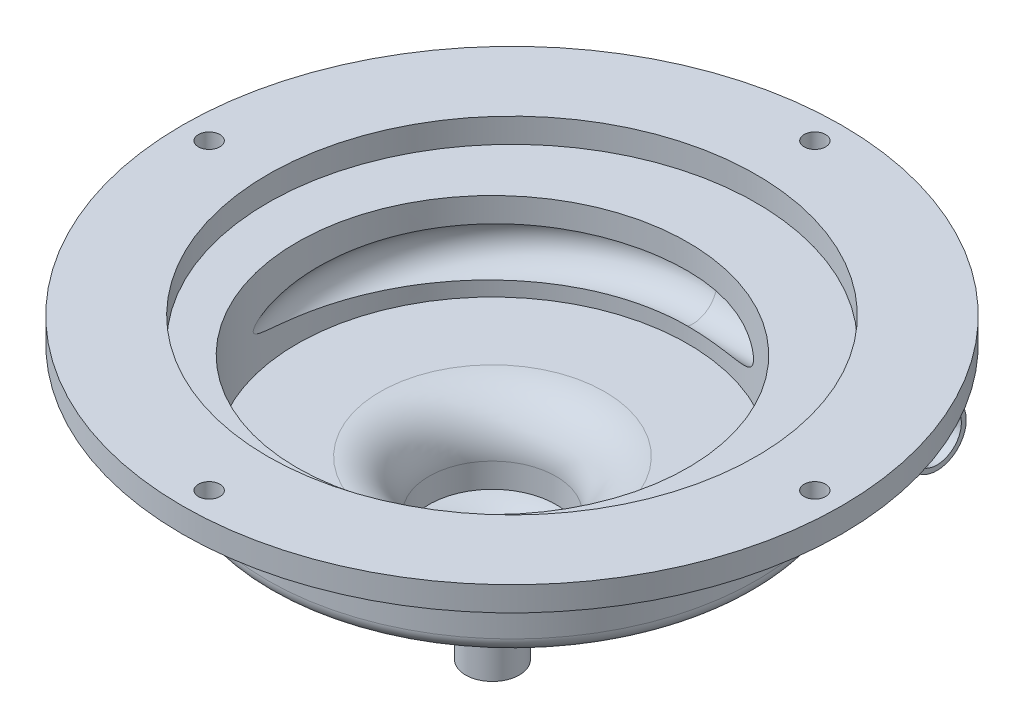
SolidWorks part; units mm, degrees
material "PLA"
ref_plane "Front Plane" through (0, 0, 0) normal (0, 0, 1) x (1, 0, 0)
ref_plane "Top Plane" through (0, 0, 0) normal (0, 1, 0) x (1, 0, 0)
ref_plane "Right Plane" through (0, 0, 0) normal (1, 0, 0) x (0, 0, -1)
sketch "Sketch1" plane through (0, 0, 0) normal (0, 1, 0) x (1, 0, 0)
  circle A0 centre (0, 0) radius 50
  circle A1 centre (0, -4) radius 40
  dimension "D1" = 4
  dimension "D2" = 80
extrude "Boss-Extrude1" add sketch "Sketch1" along normal blind 20
sketch "Sketch2" plane through (0, 0, 0) normal (0, 1, 0) x (1, 0, 0)
  circle A0 centre (0, 0) radius 50
  circle A1 centre (0, -4) radius 40
  dimension "D1" = 4
extrude "Boss-Extrude2" add sketch "Sketch2" along normal blind 2 and the other way blind 4 contours A1 region at (0, 0, 4)
sketch "Sketch3" plane through (0, 20, 0) normal (0, 1, 0) x (1, 0, 0)
  circle A0 centre (0, 0) radius 50
  circle A1 centre (0, 0) radius 67.5
  circle A2 centre (0, 62) radius 2.2
  circle A3 centre (62, 0) radius 2.2
  circle A4 centre (0, -62) radius 2.2
  circle A5 centre (-62, 0) radius 2.2
  point P15 (0, 0)
  dimension "D1" = 62
  dimension "D3" = 135
  dimension "D2" = 4
extrude "Boss-Extrude3" add sketch "Sketch3" along normal blind 5 separate body
ref_plane "Plane1" through (50, 0, 0) normal (1, 0, 0) x (0, 0, -1)
sketch "Sketch4" plane through (50, 0, 0) normal (1, 0, 0) x (0, 0, -1)
  line L0 (0, 0) -> (0, 36.7589) construction
  circle A2 centre (37, 10) radius 6
  circle A3 centre (37, 10) radius 4.75
  dimension "D1" = 12
  dimension "D2" = 9.5
  dimension "D5" = 37
  dimension "D6" = 10
  dimension "D3" = 10
  dimension "D4" = 37
sketch "Sketch5" plane through (0, 0, 0) normal (0, 1, 0) x (1, 0, 0)
  line L1 (0, 0) -> (66.027, 0) construction
  line L3 (50, 37) -> (19.8565, 37)
  point P0 (19.8565, 37)
sweep "Sweep1" add profiles "Sketch4" path "Sketch5"
sketch "Sketch6" plane through (0, 0, 0) normal (0, 1, 0) x (1, 0, 0)
  line L1 (50, -11) -> (50, 11) construction
  line L2 (50, 41) -> (50, 64.0091) construction
  line L3 (50, 41) -> (0, 41)
  arc A1 (0, 41) -> (-20.2102, -34.4256) centre (0, 0.5795) ccw
  dimension "D1" = 40.4205
  dimension "D2" = 20.2102
  dimension "D3" = 0.5795
sketch "Sketch7" plane through (50, 0, 0) normal (1, 0, 0) x (0, 0, -1)
  circle A2 centre (37, 10) radius 5
  dimension "D1" = 10
sweep "Cut-Sweep4" cut profiles "Sketch7" path "Sketch6"
sketch "Sketch9" plane through (0, -4, 0) normal (0, -1, 0) x (1, 0, 0)
  circle A0 centre (0, 4) radius 15
  circle A3 centre (0, 4) radius 40 construction
extrude "Boss-Extrude5" add sketch "Sketch9" along normal blind 15
sketch "Sketch10" plane through (0, -19, 0) normal (0, -1, 0) x (1, 0, 0)
  circle A0 centre (0, 4) radius 5.5
  circle A1 centre (0, 4) radius 15 construction
extrude "Boss-Extrude6" add sketch "Sketch10" along normal blind 15
sketch "Sketch11" plane through (0, -34, 0) normal (0, -1, 0) x (1, 0, 0)
  circle A0 centre (0, 4) radius 4.5
extrude "Cut-Extrude1" cut sketch "Sketch11" against normal through all
sketch "Sketch12" plane through (0, 2, 0) normal (0, 1, 0) x (1, 0, 0)
  circle A0 centre (0, -4) radius 13
  circle A1 centre (0, -4) radius 4.5 construction
extrude "Cut-Extrude2" cut sketch "Sketch12" against normal blind 15
fillet "Fillet1" radius 10 2 edges at (0, -13, 8.5) (0, 2, 17)
fillet "Fillet2" radius 3 3 edges at (0, -19, -11) (0, 0, 50) (0, -4, 44)
